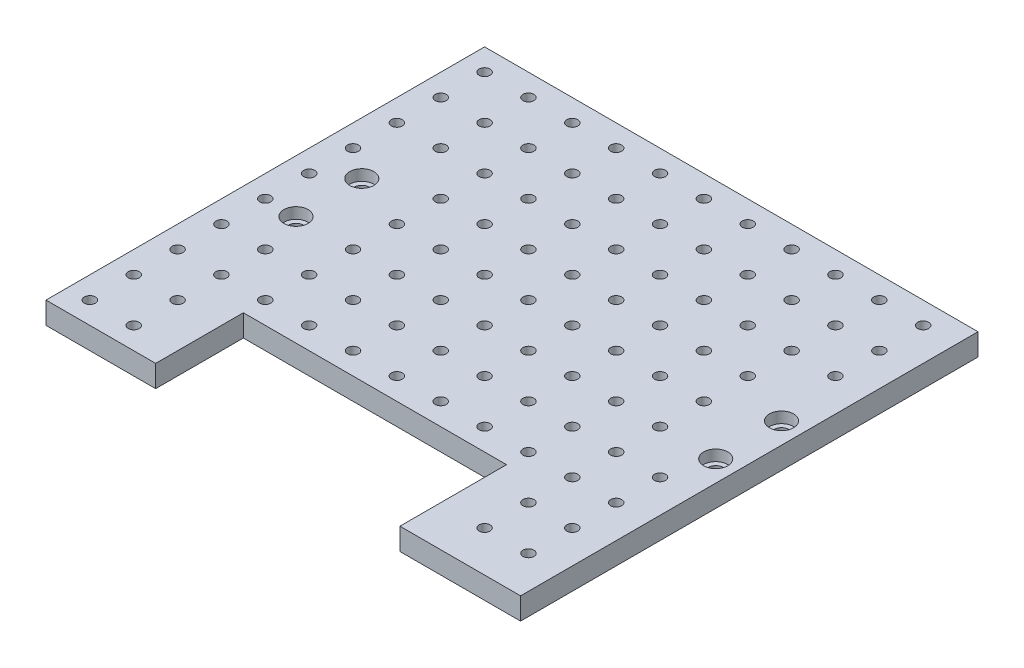
SolidWorks part; units mm, degrees
ref_plane "Front Plane" through (0, 0, 0) normal (0, 0, 1) x (1, 0, 0)
ref_plane "Top Plane" through (0, 0, 0) normal (0, 1, 0) x (1, 0, 0)
ref_plane "Right Plane" through (0, 0, 0) normal (1, 0, 0) x (0, 0, -1)
sketch "Sketch1" plane through (0, 0, 0) normal (0, 1, 0) x (1, 0, 0)
  line L1 (63.5, 0) -> (215.9, 0)
  line L2 (0, 0) -> (0, 203.2)
  line L3 (0, 203.2) -> (285.75, 203.2)
  line L4 (285.75, 0) -> (285.75, 203.2)
  line L6 (0, 0) -> (0, -50.8)
  line L7 (0, -50.8) -> (63.5, -50.8)
  line L8 (63.5, 0) -> (63.5, -50.8)
  line L10 (285.75, 0) -> (285.75, -61.722)
  line L11 (285.75, -61.722) -> (215.9, -61.722)
  line L12 (215.9, 0) -> (215.9, -61.722)
  circle A0 centre (12.7, 190.5) radius 3.175
  circle A1 centre (38.1, 190.5) radius 3.175
  circle A2 centre (63.5, 190.5) radius 3.175
  circle A3 centre (88.9, 190.5) radius 3.175
  circle A4 centre (114.3, 190.5) radius 3.175
  circle A5 centre (139.7, 190.5) radius 3.175
  circle A6 centre (165.1, 190.5) radius 3.175
  circle A7 centre (190.5, 190.5) radius 3.175
  circle A8 centre (215.9, 190.5) radius 3.175
  circle A9 centre (241.3, 190.5) radius 3.175
  circle A10 centre (266.7, 190.5) radius 3.175
  circle A11 centre (38.1, 165.1) radius 3.175
  circle A12 centre (63.5, 165.1) radius 3.175
  circle A13 centre (88.9, 165.1) radius 3.175
  circle A14 centre (114.3, 165.1) radius 3.175
  circle A15 centre (139.7, 165.1) radius 3.175
  circle A16 centre (165.1, 165.1) radius 3.175
  circle A17 centre (190.5, 165.1) radius 3.175
  circle A18 centre (215.9, 165.1) radius 3.175
  circle A19 centre (241.3, 165.1) radius 3.175
  circle A20 centre (266.7, 165.1) radius 3.175
  circle A21 centre (38.1, 139.7) radius 3.175
  circle A22 centre (63.5, 139.7) radius 3.175
  circle A23 centre (88.9, 139.7) radius 3.175
  circle A24 centre (114.3, 139.7) radius 3.175
  circle A25 centre (139.7, 139.7) radius 3.175
  circle A26 centre (165.1, 139.7) radius 3.175
  circle A27 centre (190.5, 139.7) radius 3.175
  circle A28 centre (215.9, 139.7) radius 3.175
  circle A29 centre (241.3, 139.7) radius 3.175
  circle A30 centre (266.7, 139.7) radius 3.175
  circle A32 centre (63.5, 114.3) radius 3.175
  circle A33 centre (88.9, 114.3) radius 3.175
  circle A34 centre (114.3, 114.3) radius 3.175
  circle A35 centre (139.7, 114.3) radius 3.175
  circle A36 centre (165.1, 114.3) radius 3.175
  circle A37 centre (190.5, 114.3) radius 3.175
  circle A38 centre (215.9, 114.3) radius 3.175
  circle A39 centre (241.3, 114.3) radius 3.175
  circle A42 centre (63.5, 88.9) radius 3.175
  circle A43 centre (88.9, 88.9) radius 3.175
  circle A44 centre (114.3, 88.9) radius 3.175
  circle A45 centre (139.7, 88.9) radius 3.175
  circle A46 centre (165.1, 88.9) radius 3.175
  circle A47 centre (190.5, 88.9) radius 3.175
  circle A48 centre (215.9, 88.9) radius 3.175
  circle A49 centre (241.3, 88.9) radius 3.175
  circle A52 centre (63.5, 63.5) radius 3.175
  circle A53 centre (88.9, 63.5) radius 3.175
  circle A54 centre (114.3, 63.5) radius 3.175
  circle A55 centre (139.7, 63.5) radius 3.175
  circle A56 centre (165.1, 63.5) radius 3.175
  circle A57 centre (190.5, 63.5) radius 3.175
  circle A58 centre (215.9, 63.5) radius 3.175
  circle A59 centre (241.3, 63.5) radius 3.175
  circle A61 centre (38.1, 38.1) radius 3.175
  circle A62 centre (63.5, 38.1) radius 3.175
  circle A63 centre (88.9, 38.1) radius 3.175
  circle A64 centre (114.3, 38.1) radius 3.175
  circle A65 centre (139.7, 38.1) radius 3.175
  circle A66 centre (165.1, 38.1) radius 3.175
  circle A67 centre (190.5, 38.1) radius 3.175
  circle A68 centre (215.9, 38.1) radius 3.175
  circle A69 centre (241.3, 38.1) radius 3.175
  circle A70 centre (266.7, 38.1) radius 3.175
  circle A71 centre (38.1, 12.7) radius 3.175
  circle A72 centre (63.5, 12.7) radius 3.175
  circle A73 centre (88.9, 12.7) radius 3.175
  circle A74 centre (114.3, 12.7) radius 3.175
  circle A75 centre (139.7, 12.7) radius 3.175
  circle A76 centre (165.1, 12.7) radius 3.175
  circle A77 centre (190.5, 12.7) radius 3.175
  circle A78 centre (215.9, 12.7) radius 3.175
  circle A79 centre (241.3, 12.7) radius 3.175
  circle A80 centre (266.7, 12.7) radius 3.175
  circle A81 centre (38.1, -12.7) radius 3.175
  circle A89 centre (241.3, -12.7) radius 3.175
  circle A90 centre (266.7, -12.7) radius 3.175
  circle A91 centre (38.1, -38.1) radius 3.175
  circle A99 centre (241.3, -38.1) radius 3.175
  circle A100 centre (266.7, -38.1) radius 3.175
  circle A101 centre (12.7, 165.1) radius 3.175
  circle A102 centre (12.7, 139.7) radius 3.175
  circle A103 centre (12.7, 114.3) radius 3.175
  circle A104 centre (12.7, 88.9) radius 3.175
  circle A105 centre (12.7, 63.5) radius 3.175
  circle A106 centre (12.7, 38.1) radius 3.175
  circle A107 centre (12.7, 12.7) radius 3.175
  circle A108 centre (12.7, -12.7) radius 3.175
  circle A109 centre (12.7, -38.1) radius 3.175
  circle A110 centre (88.9, -12.7) radius 3.175 [skipped]
  circle A111 centre (114.3, -12.7) radius 3.175 [skipped]
  circle A112 centre (139.7, -12.7) radius 3.175 [skipped]
  circle A113 centre (165.1, -12.7) radius 3.175 [skipped]
  circle A114 centre (190.5, -12.7) radius 3.175 [skipped]
  arc A115 (215.9, -15.875) -> (215.9, -9.525) centre (215.9, -12.7) ccw [skipped]
  arc A116 (215.9, -34.925) -> (215.9, -41.275) centre (215.9, -38.1) ccw [skipped]
  circle A117 centre (190.5, -38.1) radius 3.175 [skipped]
  circle A118 centre (165.1, -38.1) radius 3.175 [skipped]
  circle A119 centre (139.7, -38.1) radius 3.175 [skipped]
  circle A120 centre (114.3, -38.1) radius 3.175 [skipped]
  circle A121 centre (88.9, -38.1) radius 3.175 [skipped]
  arc A122 (63.5, -34.925) -> (63.5, -41.275) centre (63.5, -38.1) ccw [skipped]
  arc A123 (63.5, -9.525) -> (63.5, -15.875) centre (63.5, -12.7) ccw [skipped]
  circle A124 centre (38.1, 114.3) radius 3.175 [skipped]
  circle A125 centre (38.1, 88.9) radius 3.175 [skipped]
  circle A126 centre (266.7, 114.3) radius 3.175 [skipped]
  circle A127 centre (266.7, 88.9) radius 3.175 [skipped]
  circle A128 centre (266.7, 63.5) radius 3.175 [skipped]
  circle A129 centre (38.1, 63.5) radius 3.175 [skipped]
  dimension "D9" = 6.35
  dimension "D1" = 203.2
  dimension "D2" = 285.75
  dimension "D3" = 50.8
  dimension "D4" = 63.5
  dimension "D5" = 61.722
  dimension "D6" = 69.85
  dimension "D7" = 12.7
  dimension "D8" = 12.7
  dimension "D10" = 11
  dimension "D11" = 10
extrude "Boss-Extrude1" add sketch "Sketch1" along normal blind 12.7
sketch "Sketch2" plane through (0, 12.7, 0) normal (0, 1, 0) x (1, 0, 0)
  line L0 (0, 203.2) -> (0, -50.8) construction
  line L1 (285.75, -61.722) -> (285.75, 203.2) construction
  line L2 (285.75, 203.2) -> (0, 203.2) construction
  circle A0 centre (30.48, 101.6) radius 4.191
  circle A1 centre (30.48, 101.6) radius 6.985
  circle A2 centre (30.48, 63.5) radius 4.191
  circle A3 centre (30.48, 63.5) radius 6.985
  circle A4 centre (273.558, 101.6) radius 4.191
  circle A5 centre (273.558, 101.6) radius 6.985
  circle A6 centre (273.558, 63.5) radius 4.191
  circle A7 centre (273.558, 63.5) radius 6.985
  dimension "D1" = 8.382
  dimension "D2" = 13.97
  dimension "D3" = 38.1
  dimension "D4" = 38.1
  dimension "D5" = 30.48
  dimension "D6" = 12.192
  dimension "D7" = 101.6
extrude "Cut-Extrude1" cut sketch "Sketch2" along direction (0, 1, 0) on the side against the normal offset from surface (6.35 mm away) 6.35 contours A3 | A1 | A5 | A7 up to face at (12.7, 12.7, 15.875)
extrude "Cut-Extrude2" cut sketch "Sketch2<3>" against normal offset from surface (12.7 mm away) 12.7 contours A4 | A2 | A0 | A6 region at (30.48, 12.7, -101.6) region at (30.48, 12.7, -63.5) region at (273.558, 12.7, -101.6) up to face at (273.558, 12.7, -56.515)
sketch "Sketch2<3>" plane through (0, 12.7, 0) normal (0, 1, 0) x (1, 0, 0) same geometry as "Sketch2"
